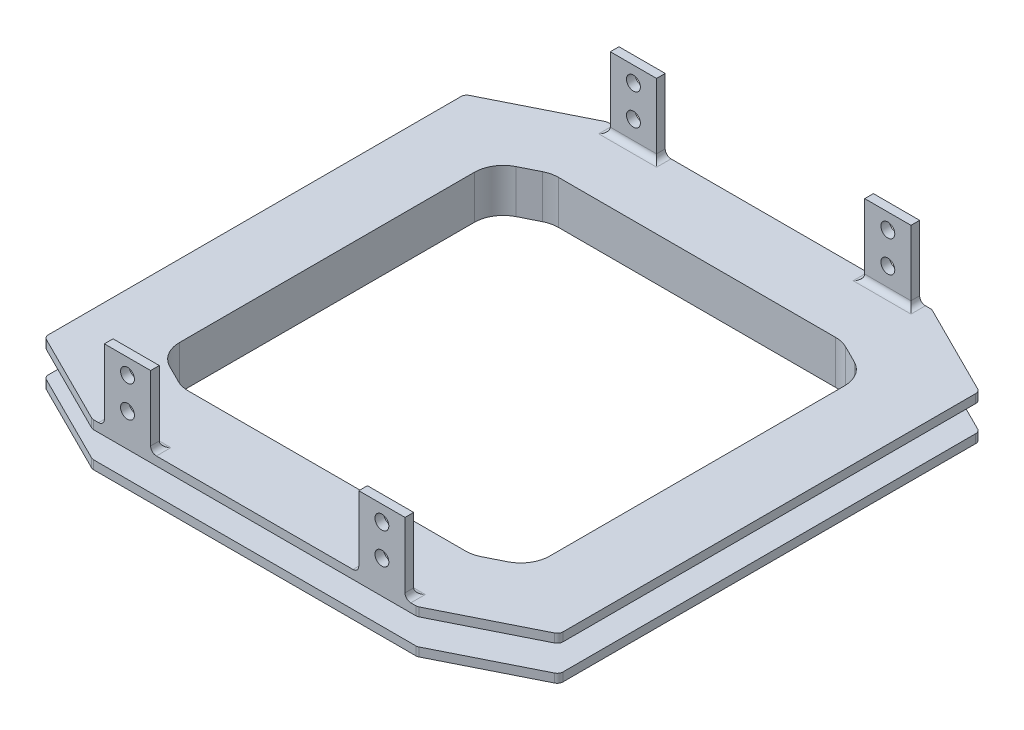
SolidWorks part; units mm, degrees
ref_plane "Front Plane" through (0, 0, 0) normal (0, 0, 1) x (1, 0, 0)
ref_plane "Top Plane" through (0, 0, 0) normal (0, 1, 0) x (1, 0, 0)
ref_plane "Right Plane" through (0, 0, 0) normal (1, 0, 0) x (0, 0, -1)
sketch "Sketch1" plane through (0, 0, 0) normal (0, 1, 0) x (1, 0, 0)
  line L5 (-33.5, 0) -> (0, 0) construction
  line L6 (-25.5, -33.5) -> (25.5, -33.5)
  line L10 (-33.5, -29.5) -> (-33.5, 29.5)
  line L11 (-25.5, 33.5) -> (25.5, 33.5)
  line L12 (33.5, -29.5) -> (33.5, 29.5)
  line L13 (0, 0) -> (0, 33.5) construction
  line L14 (25.5, -33.5) -> (33.5, -29.5)
  line L15 (25.5, 33.5) -> (33.5, 29.5)
  line L16 (-25.5, -33.5) -> (-33.5, -29.5)
  line L17 (-25.5, 33.5) -> (-33.5, 29.5)
  point P0 (0, 0)
  point P4 (33.5, -33.5)
  dimension "D3" = 4
  dimension "D2" = 8
  dimension "D4" = 67
extrude "Boss-Extrude1" add sketch "Sketch1" along normal mid plane 4.5
sketch "Sketch2" plane through (0, 2.25, 0) normal (0, 1, 0) x (1, 0, 0)
  line L16 (28.0967, -44.5) -> (44.5, -36.2984)
  line L17 (44.5, -36.2984) -> (44.5, 36.2984)
  line L18 (44.5, 36.2984) -> (28.0967, 44.5)
  line L19 (28.0967, 44.5) -> (-28.0967, 44.5)
  line L20 (-28.0967, 44.5) -> (-44.5, 36.2984)
  line L21 (-44.5, 36.2984) -> (-44.5, -36.2984)
  line L22 (-44.5, -36.2984) -> (-28.0967, -44.5)
  line L23 (-28.0967, -44.5) -> (28.0967, -44.5)
  line L24 (28.0967, -44.5) -> (44.5, -36.2984)
  line L25 (44.5, -36.2984) -> (44.5, 36.2984)
  line L26 (44.5, 36.2984) -> (28.0967, 44.5)
  line L27 (28.0967, 44.5) -> (-28.0967, 44.5)
  line L28 (-28.0967, 44.5) -> (-44.5, 36.2984)
  line L29 (-44.5, 36.2984) -> (-44.5, -36.2984)
  line L30 (-44.5, -36.2984) -> (-28.0967, -44.5)
  line L31 (-28.0967, -44.5) -> (28.0967, -44.5)
  dimension "D1" = 11
extrude "Boss-Extrude2" add sketch "Sketch2" along normal blind 1.5
mirror "Mirror1" about plane through (0, 0, 0) normal (0, 1, 0) of "Boss-Extrude2"
sketch "Sketch3" plane through (0, 0, 0) normal (0, 1, 0) x (1, 0, 0)
  line L16 (-25.1459, -32) -> (25.1459, -32)
  line L17 (25.1459, -32) -> (32, -28.5729)
  line L18 (32, -28.5729) -> (32, 28.5729)
  line L19 (32, 28.5729) -> (25.1459, 32)
  line L20 (25.1459, 32) -> (-25.1459, 32)
  line L21 (-25.1459, 32) -> (-32, 28.5729)
  line L22 (-32, 28.5729) -> (-32, -28.5729)
  line L23 (-32, -28.5729) -> (-25.1459, -32)
  line L24 (-25.1459, -32) -> (25.1459, -32)
  line L25 (25.1459, -32) -> (32, -28.5729)
  line L26 (32, -28.5729) -> (32, 28.5729)
  line L27 (32, 28.5729) -> (25.1459, 32)
  line L28 (25.1459, 32) -> (-25.1459, 32)
  line L29 (-25.1459, 32) -> (-32, 28.5729)
  line L30 (-32, 28.5729) -> (-32, -28.5729)
  line L31 (-32, -28.5729) -> (-25.1459, -32)
  dimension "D1" = 12.5
extrude "Cut-Extrude1" cut sketch "Sketch3" against normal through all both and the other way through all
sketch "Sketch5" plane through (0, 0, 0) normal (0, 0, 1) x (1, 0, 0)
  line L0 (0, 0) -> (0, 28.4264) construction
  line L1 (-28.0967, 3.75) -> (28.0967, 3.75) construction
  line L2 (-26, 3.75) -> (-18, 3.75)
  line L3 (-26, 3.75) -> (-26, 16.05)
  line L4 (-26, 16.05) -> (-18, 16.05)
  line L5 (-18, 3.75) -> (-18, 16.05)
  line L6 (-22, 16.05) -> (-22, 9.7096) construction
  line L7 (18, 3.75) -> (18, 16.05)
  line L8 (26, 16.05) -> (18, 16.05)
  line L9 (26, 3.75) -> (26, 16.05)
  line L10 (26, 3.75) -> (18, 3.75)
  dimension "D1" = 22
  dimension "D3" = 12.3
  dimension "D2" = 8
extrude "Boss-Extrude3" add sketch "Sketch5" against normal blind 1.5 from surface starting at face at (0, 3, 44.5)
extrude "Boss-Extrude4" add sketch "Sketch5<2>" along normal blind 1.5 from surface starting at face at (0, 3, -44.5)
sketch "Sketch5<2>" plane through (0, 0, 0) normal (0, 0, 1) x (1, 0, 0) same geometry as "Sketch5"
sketch "Sketch6" plane through (0, 0, 0) normal (0, 0, 1) x (1, 0, 0)
  line L0 (-22, 16.05) -> (-22, 13.35) construction
  line L1 (-18, 16.05) -> (-26, 16.05) construction
  line L2 (0, 0) -> (0, 25.5714) construction
  line L3 (22, 13.35) -> (22, 7.95) construction
  circle A0 centre (-22, 13.35) radius 1.2
  circle A1 centre (22, 13.35) radius 1.2
  circle A2 centre (22, 7.95) radius 1.2
  circle A3 centre (-22, 7.95) radius 1.2
  dimension "D1" = 2.4
  dimension "D2" = 2.7
  dimension "D3" = 5.4
extrude "Cut-Extrude3" cut sketch "Sketch6" against normal through all both and the other way through all
fillet "Fillet1" radius 1 52 edges at (33.5, 2.25, 0) (33.5, -2.25, 0) (0, 2.25, 33.5) (0, -2.25, 33.5) (0, 2.25, -33.5) (0, -2.25, -33.5) (-33.5, 2.25, 0) (-33.5, -2.25, 0) (33.5, 0, -29.5) (29.5, 2.25, -31.5) (25.5, 0, -33.5) (29.5, -2.25, -31.5) (25.5, 0, 33.5) (29.5, 2.25, 31.5) (33.5, 0, 29.5) (29.5, -2.25, 31.5) (-33.5, 0, 29.5) (-29.5, 2.25, 31.5) (-25.5, 0, 33.5) (-29.5, -2.25, 31.5) (-25.5, 0, -33.5) (-29.5, 2.25, -31.5) (-33.5, 0, -29.5) (-29.5, -2.25, -31.5) (18, 3.75, 43.75) (26, 3.75, 43.75) (22, 3.75, 43) (-18, 3.75, 43.75) (-22, 3.75, 43) (-26, 3.75, 43.75) (-22, 3.75, -43) (22, 3.75, -43) (26, 3.75, -43.75) (18, 3.75, -43.75) (-18, 3.75, -43.75) (-26, 3.75, -43.75) (28.0967, 3, -44.5) (28.0967, -3, -44.5) (44.5, 3, -36.2984) (44.5, -3, -36.2984) (44.5, 3, 36.2984) (44.5, -3, 36.2984) (28.0967, 3, 44.5) (28.0967, -3, 44.5) (-28.0967, 3, 44.5) (-28.0967, -3, 44.5) (-44.5, 3, 36.2984) (-44.5, -3, 36.2984) (-44.5, 3, -36.2984) (-44.5, -3, -36.2984) (-28.0967, -3, -44.5) (-28.0967, 3, -44.5)
fillet "Fillet2" radius 5 8 edges at (25.1459, 0, 32) (32, 0, 28.5729) (32, 0, -28.5729) (25.1459, 0, -32) (-25.1459, 0, -32) (-32, 0, -28.5729) (-25.1459, 0, 32) (-32, 0, 28.5729)
